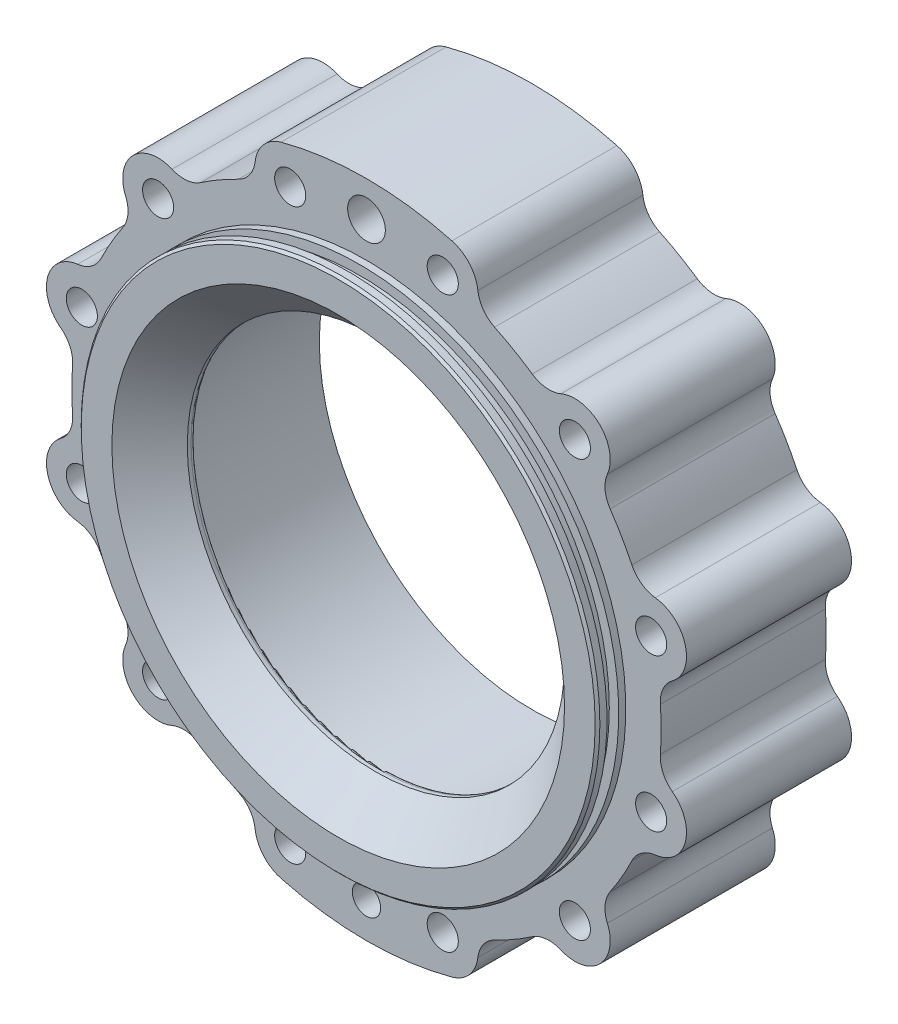
SolidWorks part; units mm, degrees
ref_plane "Front Plane" through (0, 0, 0) normal (0, 0, 1) x (1, 0, 0)
ref_plane "Top Plane" through (0, 0, 0) normal (0, 1, 0) x (1, 0, 0)
ref_plane "Right Plane" through (0, 0, 0) normal (1, 0, 0) x (0, 0, -1)
sketch "Sketch1" plane through (0, 0, 0) normal (0, 1, 0) x (1, 0, 0)
  line L0 (-55, -15.7958) -> (-55, -9.7958)
  line L2 (-55, -9.7958) -> (-70, -9.7958)
  line L3 (-55, -15.7958) -> (-40, -15.7958)
  line L4 (-40, -15.7958) -> (-40, -6)
  line L5 (-40, -6) -> (-45, -6)
  line L6 (-45, -6) -> (-45, 25.2042)
  line L7 (-45, 25.2042) -> (-70, 25.2042)
  line L8 (-70, 25.2042) -> (-70, -9.7958)
  line L12 (0, 52.7074) -> (0, -119.6493) construction
  dimension "D1" = 80
  dimension "D2" = 31.2042
  dimension "D3" = 140
  dimension "D4" = 90
  dimension "D5" = 110
  dimension "D6" = 6
revolve "Revolve1" add sketch "Sketch1" angle 360 about L12
sketch "Sketch2" plane through (0, 0, 9.7958) normal (0, 0, 1) x (1, 0, 0)
  line L0 (0, 62.5) -> (0, -62.5) construction
  circle A0 centre (0, 0) radius 62.5 construction
  circle A2 centre (0, -62.5) radius 3
  dimension "D1" = 125
  dimension "D3" = 6
extrude "Cut-Extrude1" cut sketch "Sketch2" against normal blind 9 contours A2
sketch "Sketch3" plane through (0, 0, 9.7958) normal (0, 0, 1) x (1, 0, 0)
  line L0 (0, 0) -> (0, 62.5) construction
  circle A0 centre (0, 62.5) radius 4
  dimension "D2" = 8
  dimension "D1" = 62.5
extrude "Cut-Extrude2" cut sketch "Sketch3" against normal blind 10
sketch "Bolt Holes" plane through (0, 0, 9.7958) normal (0, 0, 1) x (1, 0, 0)
  line L2 (-44.1942, 44.1942) -> (0, 0) construction
  line L3 (0, 0) -> (0, 62.5) construction
  circle A1 centre (0, 0) radius 62.5 construction
  point P0 (-60.3704, 16.1762)
  point P5 (-44.1942, 44.1942)
  point P8 (-16.1762, 60.3704)
  point P11 (16.1762, 60.3704)
  point P15 (44.1942, 44.1942)
  point P16 (60.3704, 16.1762)
  point P17 (60.3704, -16.1762)
  point P18 (44.1942, -44.1942)
  point P19 (16.1762, -60.3704)
  point P20 (-16.1762, -60.3704)
  point P21 (-44.1942, -44.1942)
  point P22 (-60.3704, -16.1762)
  point P23 (0, 0)
  point P30 (-44.1942, 44.1942)
  point P37 (44.1942, -44.1942)
  dimension "D3" = 45
  dimension "D2" = 125
  dimension "D1" = 12
sketch "Sketch9" plane through (0, 0, 0) normal (0, 1, 0) x (1, 0, 0)
  line L0 (-55, -9.7958) -> (-55, -15.7958) construction
  line L1 (-55, -13.7958) -> (-53, -13.7958)
  line L2 (-55, -13.7958) -> (-55, -11.2958)
  line L3 (-55, -11.2958) -> (-53, -11.2958)
  line L4 (-53, -13.7958) -> (-53, -11.2958)
  line L6 (0, 11.3077) -> (0, -18.9957) construction
  dimension "D1" = 2
  dimension "50" = 53
  dimension "D2" = 2.5
revolve "Oring groove" cut sketch "Sketch9" angle 360 about L6
chamfer "Chamfer1" distance 0.5 angle 45 1 edges at (-55, 0, 15.7958)
hole_wizard "M6 Clearance Hole1" positions "Bolt Holes" profile "Sketch10" hole size "M6" standard "ANSI Metric" end condition through all
sketch "Sketch10" plane through (-60.3704, 16.1762, 9.7958) normal (1, 0, 0) x (0, -1, 0)
  line L0 (0, 0) -> (0, 35)
  line L1 (0, 35) -> (3.3, 35)
  line L2 (3.3, 35) -> (3.3, 0)
  line L5 (3.3, 0) -> (0, 0)
  line L11 (0, -6.35) -> (0, 107.95) construction
  dimension "Thru Hole Dia." = 6.6
  dimension "Thru Hole Depth" = 35
fillet "Fillet2" radius 1 1 edges at (-40, 0, 6)
chamfer "Chamfer2" distance 8 angle 45 1 edges at (-40, 0, 15.7958)
sketch "Sketch11" plane through (0, 0, -25.2042) normal (0, 0, -1) x (-1, 0, 0)
  arc A0 (-64.8605, -10.1688) -> (-61.2552, -23.6238) centre (-60.3704, -16.1762) ccw
  arc A1 (-56.2858, -27.1691) -> (-61.2552, -23.6238) centre (-62.0044, -29.9295) ccw
  arc A2 (-56.2858, -27.1691) -> (-51.672, -35.1604) centre (0, 0) ccw
  arc A3 (-51.0864, -41.2367) -> (-51.672, -35.1604) centre (-56.9219, -38.7327) ccw
  arc A4 (-51.0864, -41.2367) -> (-41.2367, -51.0864) centre (-44.1942, -44.1942) ccw
  arc A5 (-35.1604, -51.672) -> (-41.2367, -51.0864) centre (-38.7327, -56.9219) ccw
  arc A6 (-35.1604, -51.672) -> (-27.1691, -56.2858) centre (0, 0) ccw
  arc A7 (-23.6238, -61.2552) -> (-27.1691, -56.2858) centre (-29.9295, -62.0044) ccw
  arc A8 (-23.6238, -61.2552) -> (-18.1173, -67.6148) centre (-16.1762, -60.3704) ccw
  arc A9 (-18.1173, -67.6148) -> (18.1173, -67.6148) centre (0, 0) ccw
  arc A10 (18.1173, -67.6148) -> (23.6238, -61.2552) centre (16.1762, -60.3704) ccw
  arc A11 (27.1691, -56.2858) -> (23.6238, -61.2552) centre (29.9295, -62.0044) ccw
  arc A12 (27.1691, -56.2858) -> (35.1604, -51.672) centre (0, 0) ccw
  arc A13 (41.2367, -51.0864) -> (35.1604, -51.672) centre (38.7327, -56.9219) ccw
  arc A14 (41.2367, -51.0864) -> (51.0864, -41.2367) centre (44.1942, -44.1942) ccw
  arc A15 (51.672, -35.1604) -> (51.0864, -41.2367) centre (56.9219, -38.7327) ccw
  arc A16 (51.672, -35.1604) -> (56.2858, -27.1691) centre (0, 0) ccw
  arc A17 (61.2552, -23.6238) -> (56.2858, -27.1691) centre (62.0044, -29.9295) ccw
  arc A18 (61.2552, -23.6238) -> (64.8605, -10.1688) centre (60.3704, -16.1762) ccw
  arc A19 (62.3295, -4.6138) -> (64.8605, -10.1688) centre (68.6621, -5.0825) ccw
  arc A20 (62.3295, -4.6138) -> (62.3295, 4.6138) centre (0, 0) ccw
  arc A21 (64.8605, 10.1688) -> (62.3295, 4.6138) centre (68.6621, 5.0825) ccw
  arc A22 (64.8605, 10.1688) -> (61.2552, 23.6238) centre (60.3704, 16.1762) ccw
  arc A23 (56.2858, 27.1691) -> (61.2552, 23.6238) centre (62.0044, 29.9295) ccw
  arc A24 (56.2858, 27.1691) -> (51.672, 35.1604) centre (0, 0) ccw
  arc A25 (51.0864, 41.2367) -> (51.672, 35.1604) centre (56.9219, 38.7327) ccw
  arc A26 (51.0864, 41.2367) -> (41.2367, 51.0864) centre (44.1942, 44.1942) ccw
  arc A27 (35.1604, 51.672) -> (41.2367, 51.0864) centre (38.7327, 56.9219) ccw
  arc A28 (35.1604, 51.672) -> (27.1691, 56.2858) centre (0, 0) ccw
  arc A29 (23.6238, 61.2552) -> (27.1691, 56.2858) centre (29.9295, 62.0044) ccw
  arc A30 (23.6238, 61.2552) -> (18.1173, 67.6148) centre (16.1762, 60.3704) ccw
  arc A31 (18.1173, 67.6148) -> (-18.1173, 67.6148) centre (0, 0) ccw
  arc A32 (-18.1173, 67.6148) -> (-23.6238, 61.2552) centre (-16.1762, 60.3704) ccw
  arc A33 (-27.1691, 56.2858) -> (-23.6238, 61.2552) centre (-29.9295, 62.0044) ccw
  arc A34 (-27.1691, 56.2858) -> (-35.1604, 51.672) centre (0, 0) ccw
  arc A35 (-41.2367, 51.0864) -> (-35.1604, 51.672) centre (-38.7327, 56.9219) ccw
  arc A36 (-41.2367, 51.0864) -> (-51.0864, 41.2367) centre (-44.1942, 44.1942) ccw
  arc A37 (-51.672, 35.1604) -> (-51.0864, 41.2367) centre (-56.9219, 38.7327) ccw
  arc A38 (-51.672, 35.1604) -> (-56.2858, 27.1691) centre (0, 0) ccw
  arc A39 (-61.2552, 23.6238) -> (-56.2858, 27.1691) centre (-62.0044, 29.9295) ccw
  arc A40 (-61.2552, 23.6238) -> (-64.8605, 10.1688) centre (-60.3704, 16.1762) ccw
  arc A41 (-62.3295, 4.6138) -> (-64.8605, 10.1688) centre (-68.6621, 5.0825) ccw
  arc A42 (-62.3295, 4.6138) -> (-62.3295, -4.6138) centre (0, 0) ccw
  arc A43 (-64.8605, -10.1688) -> (-62.3295, -4.6138) centre (-68.6621, -5.0825) ccw
  circle A44 centre (0, 0) radius 70 construction
  circle A45 centre (0, 0) radius 70
  circle M57 centre (0, 0) radius 70
extrude "Cut-Extrude3" cut sketch "Sketch11" against normal through all contours A30 A29 A28 A27 A26 M57 | A26 A25 A24 A23 A22 M57 | A22 A21 A20 A19 A18 M57 | A18 A17 A16 A15 A14 M57 | A14 A13 A12 A11 A10 M57 | A8 A7 A6 A5 A4 M57 | A4 A3 A2 A1 A0 M57 | A0 A43 A42 A41 A40 M57 | A40 A39 A38 A37 A36 M57 | A36 A35 A34 A33 A32 M57 region at (66.4201, 0, -25.2042) region at (57.5215, -33.21, -25.2042) region at (57.5215, 33.21, -25.2042) region at (33.21, -57.5215, -25.2042) region at (33.21, 57.5215, -25.2042) region at (-33.21, -57.5215, -25.2042) region at (-33.21, 57.5215, -25.2042) region at (-57.5215, -33.21, -25.2042) region at (-57.5215, 33.21, -25.2042) region at (-66.4201, 0, -25.2042)
